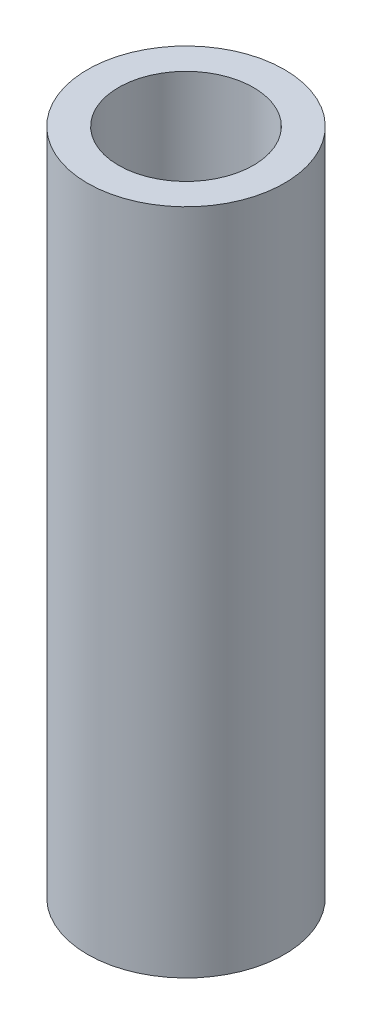
SolidWorks part; units mm, degrees
ref_plane "Piano frontale" through (0, 0, 0) normal (0, 0, 1) x (1, 0, 0)
ref_plane "Piano superiore" through (0, 0, 0) normal (0, 1, 0) x (1, 0, 0)
ref_plane "Piano destro" through (0, 0, 0) normal (1, 0, 0) x (0, 0, -1)
sketch "Schizzo1" plane through (0, 0, 0) normal (0, 0, 1) x (1, 0, 0)
  line L0 (0, 0) -> (0, 21.5308)
  point P3 (0, 0)
  point P4 (0, 21.5308)
  point P5 (0, 0)
sweep "Sweep-Sottile1" add path "Schizzo1" circular profile diameter 6.35 parameters "D1"=1, "D3"=6.35
